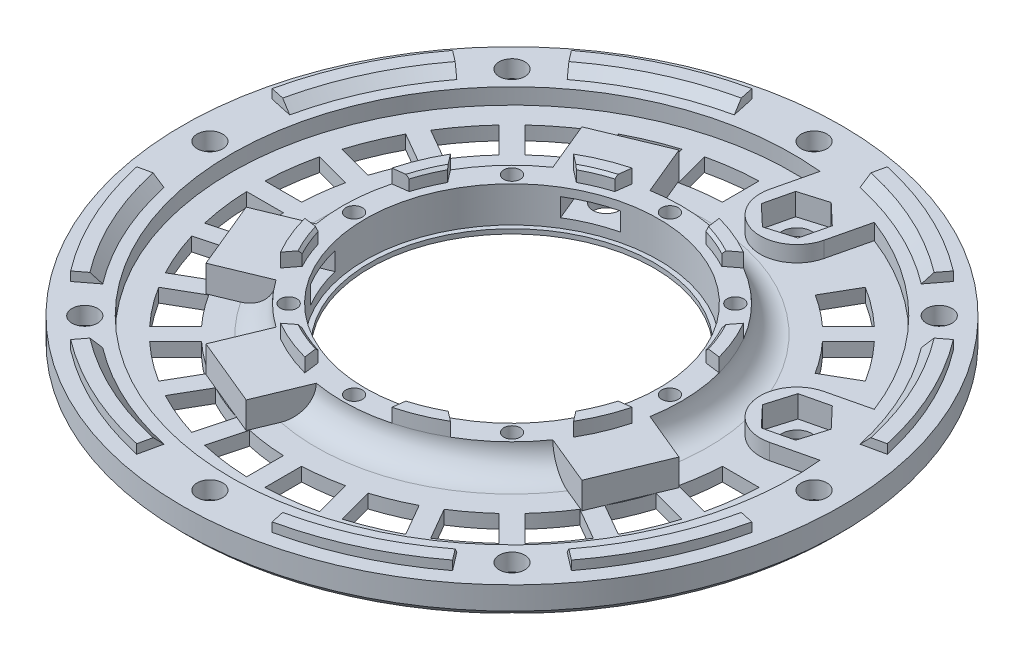
SolidWorks part; units mm, degrees
ref_plane "Front Plane" through (0, 0, 0) normal (0, 0, 1) x (1, 0, 0)
ref_plane "Top Plane" through (0, 0, 0) normal (0, 1, 0) x (1, 0, 0)
ref_plane "Right Plane" through (0, 0, 0) normal (1, 0, 0) x (0, 0, -1)
sketch "Sketch1" plane through (0, 0, 0) normal (0, 1, 0) x (1, 0, 0)
  circle A0 centre (0, 0) radius 16.025
  circle A1 centre (0, 0) radius 36
  dimension "D1" = 32.05
  dimension "D2" = 72
extrude "Boss-Extrude1" add sketch "Sketch1" along normal blind 1
sketch "Sketch2" plane through (0, 0, 0) normal (0, -1, 0) x (1, 0, 0)
  circle A0 centre (0, 0) radius 17.25 construction
  circle A1 centre (0, 0) radius 18.5 construction
  circle A2 centre (0, 0) radius 18.5
  circle A3 centre (0, 0) radius 16.025 construction
  circle A4 centre (0, 0) radius 16.025
  arc A5 (-1.2, 18.461) -> (-4.705, 17.8917) centre (0, 0) ccw construction
  point P3 (0, -17.25)
extrude "Boss-Extrude2" add sketch "Sketch2" against normal offset from surface (3.9 mm away) 3.9 up to face at (0, 0, 36)
fillet "Fillet1" radius 2.9 1 edges at (0, 1, 18.5)
sketch "Sketch4" plane through (0, 0, 0) normal (0, 1, 0) x (1, 0, 0)
  circle A0 centre (0, 0) radius 15.525
  circle A1 centre (0, 0) radius 36
  circle A2 centre (0, 0) radius 36
  circle A3 centre (0, 0) radius 16.025 construction
  dimension "D2" = 0.5
  dimension "D1" = 0
extrude "Boss-Extrude3" add sketch "Sketch4" against normal blind 0.5
sketch "Sketch5" plane through (0, 1, 0) normal (0, 1, 0) x (1, 0, 0)
  line L0 (27.99, -0.75) -> (19.9859, -0.75) construction
  line L1 (19.9859, 0.75) -> (27.99, 0.75) construction
  line L2 (27.99, -0.75) -> (19.9859, -0.75) construction
  line L3 (19.9859, 0.75) -> (27.99, 0.75) construction
  line L4 (0, 0) -> (36, 0) construction
  line L5 (0, 0) -> (34.7733, 9.3175) construction
  line L6 (34.7733, 9.3175) -> (36, 0) construction
  line L7 (0, 0) -> (35.3867, 4.6587) construction
  line L8 (27.99, 1) -> (23.9792, 1)
  line L9 (27.295, 6.2784) -> (23.4209, 5.2403)
  line L10 (27.99, -1) -> (23.9792, -1)
  line L11 (27.295, -6.2784) -> (23.4209, -5.2403)
  line L12 (26.7774, -8.2103) -> (22.9033, -7.1722)
  line L13 (24.74, -13.129) -> (21.2666, -11.1236)
  line L14 (23.74, -14.861) -> (20.2666, -12.8556)
  line L15 (20.499, -19.0848) -> (17.6629, -16.2487)
  line L16 (19.0848, -20.499) -> (16.2487, -17.6629)
  line L17 (14.861, -23.74) -> (12.8556, -20.2666)
  line L18 (13.129, -24.74) -> (11.1236, -21.2666)
  line L19 (8.2103, -26.7774) -> (7.1722, -22.9033)
  line L20 (6.2784, -27.295) -> (5.2403, -23.4209)
  line L21 (1, -27.99) -> (1, -23.9792)
  line L22 (-1, -27.99) -> (-1, -23.9792)
  line L23 (-6.2784, -27.295) -> (-5.2403, -23.4209)
  line L24 (-8.2103, -26.7774) -> (-7.1722, -22.9033)
  line L25 (-13.129, -24.74) -> (-11.1236, -21.2666)
  line L26 (-14.861, -23.74) -> (-12.8556, -20.2666)
  line L27 (-19.0848, -20.499) -> (-16.2487, -17.6629)
  line L28 (-20.499, -19.0848) -> (-17.6629, -16.2487)
  line L29 (-23.74, -14.861) -> (-20.2666, -12.8556)
  line L30 (-24.74, -13.129) -> (-21.2666, -11.1236)
  line L31 (-26.7774, -8.2103) -> (-22.9033, -7.1722)
  line L32 (-27.295, -6.2784) -> (-23.4209, -5.2403)
  line L33 (-27.99, -1) -> (-23.9792, -1)
  line L34 (-27.99, 1) -> (-23.9792, 1)
  line L35 (-27.295, 6.2784) -> (-23.4209, 5.2403)
  line L36 (-26.7774, 8.2103) -> (-22.9033, 7.1722)
  line L37 (-24.74, 13.129) -> (-21.2666, 11.1236)
  line L38 (-23.74, 14.861) -> (-20.2666, 12.8556)
  line L39 (-20.499, 19.0848) -> (-17.6629, 16.2487)
  line L40 (-19.0848, 20.499) -> (-16.2487, 17.6629)
  line L41 (-14.861, 23.74) -> (-12.8556, 20.2666)
  line L42 (-13.129, 24.74) -> (-11.1236, 21.2666)
  line L43 (-8.2103, 26.7774) -> (-7.1722, 22.9033)
  line L44 (-6.2784, 27.295) -> (-5.2403, 23.4209)
  line L45 (-1, 27.99) -> (-1, 23.9792)
  line L46 (1, 27.99) -> (1, 23.9792)
  line L47 (6.2784, 27.295) -> (5.2403, 23.4209)
  line L48 (8.2103, 26.7774) -> (7.1722, 22.9033)
  line L49 (13.129, 24.74) -> (11.1236, 21.2666)
  line L50 (14.861, 23.74) -> (12.8556, 20.2666)
  line L51 (19.0848, 20.499) -> (16.2487, 17.6629)
  line L52 (20.499, 19.0848) -> (17.6629, 16.2487)
  line L53 (23.74, 14.861) -> (20.2666, 12.8556)
  line L54 (24.74, 13.129) -> (21.2666, 11.1236)
  line L55 (26.7774, 8.2103) -> (22.9033, 7.1722)
  line L56 (0, 0) -> (23.9792, 1) construction
  circle A0 centre (0, 0) radius 24 construction
  circle A2 centre (0, 0) radius 36 construction
  arc A3 (23.9792, 1) -> (23.4209, 5.2403) centre (0, 0) ccw
  arc A4 (27.99, 1) -> (27.295, 6.2784) centre (0, 0) ccw
  arc A5 (27.295, -6.2784) -> (27.99, -1) centre (0, 0) ccw
  arc A6 (23.4209, -5.2403) -> (23.9792, -1) centre (0, 0) ccw
  arc A7 (24.74, -13.129) -> (26.7774, -8.2103) centre (0, 0) ccw
  arc A8 (21.2666, -11.1236) -> (22.9033, -7.1722) centre (0, 0) ccw
  arc A9 (20.499, -19.0848) -> (23.74, -14.861) centre (0, 0) ccw
  arc A10 (17.6629, -16.2487) -> (20.2666, -12.8556) centre (0, 0) ccw
  arc A11 (14.861, -23.74) -> (19.0848, -20.499) centre (0, 0) ccw
  arc A12 (12.8556, -20.2666) -> (16.2487, -17.6629) centre (0, 0) ccw
  arc A13 (8.2103, -26.7774) -> (13.129, -24.74) centre (0, 0) ccw
  arc A14 (7.1722, -22.9033) -> (11.1236, -21.2666) centre (0, 0) ccw
  arc A15 (1, -27.99) -> (6.2784, -27.295) centre (0, 0) ccw
  arc A16 (1, -23.9792) -> (5.2403, -23.4209) centre (0, 0) ccw
  arc A17 (-6.2784, -27.295) -> (-1, -27.99) centre (0, 0) ccw
  arc A18 (-5.2403, -23.4209) -> (-1, -23.9792) centre (0, 0) ccw
  arc A19 (-13.129, -24.74) -> (-8.2103, -26.7774) centre (0, 0) ccw
  arc A20 (-11.1236, -21.2666) -> (-7.1722, -22.9033) centre (0, 0) ccw
  arc A21 (-19.0848, -20.499) -> (-14.861, -23.74) centre (0, 0) ccw
  arc A22 (-16.2487, -17.6629) -> (-12.8556, -20.2666) centre (0, 0) ccw
  arc A23 (-23.74, -14.861) -> (-20.499, -19.0848) centre (0, 0) ccw
  arc A24 (-20.2666, -12.8556) -> (-17.6629, -16.2487) centre (0, 0) ccw
  arc A25 (-26.7774, -8.2103) -> (-24.74, -13.129) centre (0, 0) ccw
  arc A26 (-22.9033, -7.1722) -> (-21.2666, -11.1236) centre (0, 0) ccw
  arc A27 (-27.99, -1) -> (-27.295, -6.2784) centre (0, 0) ccw
  arc A28 (-23.9792, -1) -> (-23.4209, -5.2403) centre (0, 0) ccw
  arc A29 (-27.295, 6.2784) -> (-27.99, 1) centre (0, 0) ccw
  arc A30 (-23.4209, 5.2403) -> (-23.9792, 1) centre (0, 0) ccw
  arc A31 (-24.74, 13.129) -> (-26.7774, 8.2103) centre (0, 0) ccw
  arc A32 (-21.2666, 11.1236) -> (-22.9033, 7.1722) centre (0, 0) ccw
  arc A33 (-20.499, 19.0848) -> (-23.74, 14.861) centre (0, 0) ccw
  arc A34 (-17.6629, 16.2487) -> (-20.2666, 12.8556) centre (0, 0) ccw
  arc A35 (-14.861, 23.74) -> (-19.0848, 20.499) centre (0, 0) ccw
  arc A36 (-12.8556, 20.2666) -> (-16.2487, 17.6629) centre (0, 0) ccw
  arc A37 (-8.2103, 26.7774) -> (-13.129, 24.74) centre (0, 0) ccw
  arc A38 (-7.1722, 22.9033) -> (-11.1236, 21.2666) centre (0, 0) ccw
  arc A39 (-1, 27.99) -> (-6.2784, 27.295) centre (0, 0) ccw
  arc A40 (-1, 23.9792) -> (-5.2403, 23.4209) centre (0, 0) ccw
  arc A41 (6.2784, 27.295) -> (1, 27.99) centre (0, 0) ccw
  arc A42 (5.2403, 23.4209) -> (1, 23.9792) centre (0, 0) ccw
  arc A43 (13.129, 24.74) -> (8.2103, 26.7774) centre (0, 0) ccw
  arc A44 (11.1236, 21.2666) -> (7.1722, 22.9033) centre (0, 0) ccw
  arc A45 (19.0848, 20.499) -> (14.861, 23.74) centre (0, 0) ccw
  arc A46 (16.2487, 17.6629) -> (12.8556, 20.2666) centre (0, 0) ccw
  arc A47 (23.74, 14.861) -> (20.499, 19.0848) centre (0, 0) ccw
  arc A48 (20.2666, 12.8556) -> (17.6629, 16.2487) centre (0, 0) ccw
  arc A49 (26.7774, 8.2103) -> (24.74, 13.129) centre (0, 0) ccw
  arc A50 (22.9033, 7.1722) -> (21.2666, 11.1236) centre (0, 0) ccw
  dimension "D1" = 15
  dimension "D2" = 1
  dimension "D4" = 24
  dimension "D3" = 24
extrude "Cut-Extrude1" cut sketch "Sketch5" against normal through all both and the other way through all
sketch "Sketch7" plane through (0, 3.9, 0) normal (0, 1, 0) x (1, 0, 0)
  line L0 (0, 0) -> (0, 17.25) construction
  circle A0 centre (0, 17.25) radius 0.9
  circle A1 centre (12.1976, 12.1976) radius 0.9
  circle A2 centre (17.25, 0) radius 0.9
  circle A3 centre (12.1976, -12.1976) radius 0.9
  circle A4 centre (0, -17.25) radius 0.9
  circle A5 centre (-12.1976, -12.1976) radius 0.9
  circle A6 centre (-17.25, 0) radius 0.9
  circle A7 centre (-12.1976, 12.1976) radius 0.9
  point P21 (0, 0)
  dimension "D1" = 1.8
  dimension "D2" = 8
extrude "Cut-Extrude2" cut sketch "Sketch7" against normal through all
sketch "Sketch8" plane through (0, 1, 0) normal (0, 1, 0) x (1, 0, 0)
  arc A0 (-30.6392, -0.8144) -> (-29.9521, -6.5032) centre (0, 0) ccw construction
  arc A1 (-30.6392, -0.8144) -> (-29.9521, -6.5032) centre (0, 0) ccw construction
  arc A2 (-29.9521, 6.5032) -> (-30.6392, 0.8144) centre (0, 0) ccw construction
  arc A3 (-29.9521, 6.5032) -> (-30.6392, 0.8144) centre (0, 0) ccw construction
  circle A5 centre (0, 0) radius 30.65
  circle A6 centre (0, 0) radius 36 construction
  circle A7 centre (0, 0) radius 36
extrude "Boss-Extrude4" add sketch "Sketch8" along normal blind 1.7378
sketch "Sketch9" plane through (0, 2.7378, 0) normal (0, 1, 0) x (1, 0, 0)
  line L0 (0, 0) -> (-29.9521, 6.5032) construction
  line L1 (0, 0) -> (-29.9521, -6.5032) construction
  line L2 (-29.9521, 6.5032) -> (-29.9521, -6.5032) construction
  line L3 (-27.3707, 21.0023) -> (-23.9196, 18.3542) construction
  line L4 (0, 0) -> (0, 36) construction
  line L5 (0, 0) -> (-25.4558, 25.4558) construction
  line L6 (-24.3163, 18.6585) -> (0, 0) construction
  line L7 (-24.3163, 18.6585) -> (-28.5607, 21.9154) construction
  line L8 (-29.9521, 6.5032) -> (-35.1803, 7.6384) construction
  line L9 (-27.3521, 20.862) -> (-25.3687, 19.3401)
  line L10 (-31.2086, 14.47) -> (0, 0) construction
  line L11 (-33.5954, 7.3966) -> (-31.1523, 6.8662)
  line L12 (-7.3966, 33.5954) -> (-6.8662, 31.1523)
  line L13 (-20.862, 27.3521) -> (-19.3401, 25.3687)
  arc A0 (-29.9521, 6.5032) -> (-24.3163, 18.6585) centre (0, 0) cw construction
  arc A1 (-35.1803, 7.6384) -> (-28.5607, 21.9154) centre (0, 0) cw construction
  circle A2 centre (0, 0) radius 36 construction
  circle A3 centre (0, 0) radius 30.65 construction
  arc A4 (-27.2914, 20.9414) -> (-33.6168, 7.2989) centre (0, 0) ccw construction
  arc A5 (-31.1523, 6.8662) -> (-25.3687, 19.3401) centre (0, 0) cw
  arc A6 (-33.5954, 7.3966) -> (-27.3521, 20.862) centre (0, 0) cw
  circle A7 centre (0, 0) radius 36 construction
  arc A8 (-6.8662, 31.1523) -> (-19.3401, 25.3687) centre (0, 0) ccw
  arc A9 (-7.3966, 33.5954) -> (-20.862, 27.3521) centre (0, 0) ccw
  dimension "D2" = 0.1
  dimension "D3" = 45
  dimension "D4" = 0.1
  dimension "D1" = 2.5
extrude "Boss-Extrude5" add sketch "Sketch9" along normal blind 1
ref_axis "Axis1" through (0, -0.72, 0) along (0, 1, 0)
pattern_circular "CirPattern1" count 4 over 360 about axis through (0, -0.72, 0) along (0, 1, 0) of "Boss-Extrude5"
chamfer "Chamfer1" distance 1 angle 45 8 edges at (-28.9406, 3.7378, -13.4184) (-13.4184, 3.7378, -28.9406) (13.4184, 3.7378, -28.9406) (28.9406, 3.7378, -13.4184) (28.9406, 3.7378, 13.4184) (13.4184, 3.7378, 28.9406) (-13.4184, 3.7378, 28.9406) (-28.9406, 3.7378, 13.4184)
sketch "Sketch10" plane through (0, 2.7378, 0) normal (0, 1, 0) x (1, 0, 0)
  line L0 (0, 0) -> (0, 36) construction
  circle A0 centre (0, 0) radius 36 construction
  circle A1 centre (0, 33) radius 1.4 construction
  circle A2 centre (0, 33) radius 1.4
  circle A3 centre (23.3345, 23.3345) radius 1.4
  circle A4 centre (33, 0) radius 1.4
  circle A5 centre (23.3345, -23.3345) radius 1.4
  circle A6 centre (0, -33) radius 1.4
  circle A7 centre (-23.3345, -23.3345) radius 1.4
  circle A8 centre (-33, 0) radius 1.4
  circle A9 centre (-23.3345, 23.3345) radius 1.4
  point P26 (0, 0)
  dimension "D1" = 8
extrude "Cut-Extrude3" cut sketch "Sketch10" against normal through all both and the other way through all
chamfer "Chamfer2" distance 0.75 angle 45 1 edges at (0, -0.5, 36)
hole_wizard "CSK for M2.5 Flat Head Machine Screw1" positions "Sketch11" profile "Sketch12" countersink size "M2.5" standard "ANSI Metric" end condition through all
sketch "Sketch11" plane through (0, -0.5, 0) normal (0, -1, 0) x (-1, 0, 0)
  point P0 (0, -33)
  point P3 (23.3345, -23.3345)
  point P6 (33, 0)
  point P9 (23.3345, 23.3345)
  point P12 (0, 33)
  point P15 (-23.3345, 23.3345)
  point P18 (-33, 0)
  point P21 (-23.3345, -23.3345)
sketch "Sketch12" plane through (0, -0.5, 33) normal (1, 0, 0) x (0, 0, -1)
  line L0 (0, 0) -> (0, 4.4)
  line L1 (0, 4.4) -> (1.35, 4.4)
  line L2 (1.35, 4.4) -> (1.35, 1.4)
  line L3 (1.35, 1.4) -> (2.75, 0)
  line L5 (2.75, 0) -> (0, 0)
  line L6 (-1.35, 1.4) -> (-2.75, 0) construction
  line L11 (0, -6.35) -> (0, 107.95) construction
  dimension "Thru Hole Dia." = 2.7
  dimension "Thru Hole Depth" = 4.4
  dimension "Near C'Sink Dia." = 5.5
  dimension "Near C'Sink Angle" = 90
sketch "Sketch13" plane through (0, 3.9, 0) normal (0, 1, 0) x (1, 0, 0)
  line L0 (0, 0) -> (-7.0796, 17.0918) construction
  line L1 (0, 0) -> (0, 18.5) construction
  line L2 (-9.2808, 16.0037) -> (-7.9403, 14.9751)
  line L3 (-4.7538, 17.8788) -> (-4.9743, 16.2037)
  line L4 (4.7538, 17.8788) -> (4.9743, 16.2037)
  line L5 (9.2808, 16.0037) -> (7.9403, 14.9751)
  line L6 (16.0037, 9.2808) -> (14.9751, 7.9403)
  line L7 (17.8788, 4.7538) -> (16.2037, 4.9743)
  line L8 (17.8788, -4.7538) -> (16.2037, -4.9743)
  line L9 (16.0037, -9.2808) -> (14.9751, -7.9403)
  line L10 (9.2808, -16.0037) -> (7.9403, -14.9751)
  line L11 (4.7538, -17.8788) -> (4.9743, -16.2037)
  line L12 (-4.7538, -17.8788) -> (-4.9743, -16.2037)
  line L13 (-9.2808, -16.0037) -> (-7.9403, -14.9751)
  line L14 (-16.0037, -9.2808) -> (-14.9751, -7.9403)
  line L15 (-17.8788, -4.7538) -> (-16.2037, -4.9743)
  line L16 (-17.8788, 4.7538) -> (-16.2037, 4.9743)
  line L17 (-16.0037, 9.2808) -> (-14.9751, 7.9403)
  circle A0 centre (0, 0) radius 18.5 construction
  arc A1 (-7.9403, 14.9751) -> (-4.9743, 16.2037) centre (0, 0) cw
  arc A2 (-9.2808, 16.0037) -> (-4.7538, 17.8788) centre (0, 0) cw
  arc A3 (4.9743, 16.2037) -> (7.9403, 14.9751) centre (0, 0) cw
  arc A4 (4.7538, 17.8788) -> (9.2808, 16.0037) centre (0, 0) cw
  arc A5 (14.9751, 7.9403) -> (16.2037, 4.9743) centre (0, 0) cw
  arc A6 (16.0037, 9.2808) -> (17.8788, 4.7538) centre (0, 0) cw
  arc A7 (16.2037, -4.9743) -> (14.9751, -7.9403) centre (0, 0) cw
  arc A8 (17.8788, -4.7538) -> (16.0037, -9.2808) centre (0, 0) cw
  arc A9 (7.9403, -14.9751) -> (4.9743, -16.2037) centre (0, 0) cw
  arc A10 (9.2808, -16.0037) -> (4.7538, -17.8788) centre (0, 0) cw
  arc A11 (-4.9743, -16.2037) -> (-7.9403, -14.9751) centre (0, 0) cw
  arc A12 (-4.7538, -17.8788) -> (-9.2808, -16.0037) centre (0, 0) cw
  arc A13 (-14.9751, -7.9403) -> (-16.2037, -4.9743) centre (0, 0) cw
  arc A14 (-16.0037, -9.2808) -> (-17.8788, -4.7538) centre (0, 0) cw
  arc A15 (-16.2037, 4.9743) -> (-14.9751, 7.9403) centre (0, 0) cw
  arc A16 (-17.8788, 4.7538) -> (-16.0037, 9.2808) centre (0, 0) cw
  point P12 (-6.4865, 15.6598)
  point P20 (6.4865, 15.6598)
  point P25 (15.6598, 6.4865)
  point P30 (15.6598, -6.4865)
  point P35 (6.4865, -15.6598)
  point P40 (-6.4865, -15.6598)
  point P45 (-15.6598, -6.4865)
  point P50 (-15.6598, 6.4865)
  point P51 (0, 0)
  dimension "D1" = 22.5
  dimension "D2" = 30
  dimension "D3" = 1.55
  dimension "D4" = 4.9
  dimension "D5" = 8
extrude "Boss-Extrude6" add sketch "Sketch13" along normal blind 1.5
chamfer "Chamfer3" distance 0.3 angle 45 8 edges at (-15.6598, 5.4, -6.4865) (-15.6598, 5.4, 6.4865) (-6.4865, 5.4, 15.6598) (6.4865, 5.4, 15.6598) (15.6598, 5.4, 6.4865) (15.6598, 5.4, -6.4865) (6.4865, 5.4, -15.6598) (-6.4865, 5.4, -15.6598)
sketch "Sketch14" plane through (0, -0.5, 0) normal (0, -1, 0) x (1, 0, 0)
  line L0 (0, 0) -> (25.4558, -25.4558) construction
  line L1 (0, 0) -> (0, -36) construction
  line L6 (0, 0) -> (-22.1731, 9.1844) construction
  line L7 (0, 0) -> (-9.1844, -22.1731) construction
  circle A0 centre (0, 0) radius 36 construction
  circle A1 centre (0, 0) radius 16.025 construction
  arc A5 (-21.2666, 11.1236) -> (-22.9033, 7.1722) centre (0, 0) ccw construction
  circle A6 centre (-17.5768, 7.2806) radius 1.45
  circle A7 centre (-17.5768, 7.2806) radius 4.975 construction
  arc A8 (-11.1236, -21.2666) -> (-7.1722, -22.9033) centre (0, 0) ccw construction
  circle A9 centre (-7.2806, -17.5768) radius 1.45
  circle A10 centre (-7.2806, -17.5768) radius 4.975 construction
  circle A11 centre (17.5768, 7.2806) radius 1.45
  circle A12 centre (-7.2806, 17.5768) radius 1.45
  point P24 (0, 0)
  point P25 (-14.8052, 6.1325)
  point P28 (-16.2372, 6.7257)
  dimension "D2" = 2.9
  dimension "D3" = 3
  dimension "D1" = 45
sketch "Sketch15" plane through (0, 1, 0) normal (0, 1, 0) x (1, 0, 0)
  line L0 (-9.8825, 13.2519) -> (-12.8979, 20.5316)
  line L1 (-9.8825, 13.2519) -> (-2.3825, 16.3585)
  line L2 (-12.8979, 20.5316) -> (-5.3979, 23.6382)
  line L3 (-2.3825, 16.3585) -> (-5.3979, 23.6382)
  line L4 (-9.8825, 13.2519) -> (-5.3979, 23.6382) construction
  line L5 (-12.8979, 20.5316) -> (-2.3825, 16.3585) construction
  line L6 (0, 0) -> (-9.1844, 22.1731) construction
  line L7 (2.3825, 16.3585) -> (5.3979, 23.6382) [skipped]
  line L8 (2.3825, 16.3585) -> (9.8825, 13.2519) [skipped]
  line L9 (5.3979, 23.6382) -> (12.8979, 20.5316) [skipped]
  line L10 (9.8825, 13.2519) -> (12.8979, 20.5316) [skipped]
  line L11 (2.3825, 16.3585) -> (12.8979, 20.5316) construction
  line L12 (5.3979, 23.6382) -> (9.8825, 13.2519) construction
  line L13 (13.2519, 9.8825) -> (20.5316, 12.8979) [skipped]
  line L14 (13.2519, 9.8825) -> (16.3585, 2.3825) [skipped]
  line L15 (20.5316, 12.8979) -> (23.6382, 5.3979) [skipped]
  line L16 (16.3585, 2.3825) -> (23.6382, 5.3979) [skipped]
  line L17 (13.2519, 9.8825) -> (23.6382, 5.3979) construction
  line L18 (20.5316, 12.8979) -> (16.3585, 2.3825) construction
  line L19 (16.3585, -2.3825) -> (23.6382, -5.3979)
  line L20 (16.3585, -2.3825) -> (13.2519, -9.8825)
  line L21 (23.6382, -5.3979) -> (20.5316, -12.8979)
  line L22 (13.2519, -9.8825) -> (20.5316, -12.8979)
  line L23 (16.3585, -2.3825) -> (20.5316, -12.8979) construction
  line L24 (23.6382, -5.3979) -> (13.2519, -9.8825) construction
  line L25 (9.8825, -13.2519) -> (12.8979, -20.5316) [skipped]
  line L26 (9.8825, -13.2519) -> (2.3825, -16.3585) [skipped]
  line L27 (12.8979, -20.5316) -> (5.3979, -23.6382) [skipped]
  line L28 (2.3825, -16.3585) -> (5.3979, -23.6382) [skipped]
  line L29 (9.8825, -13.2519) -> (5.3979, -23.6382) construction
  line L30 (12.8979, -20.5316) -> (2.3825, -16.3585) construction
  line L31 (-2.3825, -16.3585) -> (-5.3979, -23.6382)
  line L32 (-2.3825, -16.3585) -> (-9.8825, -13.2519)
  line L33 (-5.3979, -23.6382) -> (-12.8979, -20.5316)
  line L34 (-9.8825, -13.2519) -> (-12.8979, -20.5316)
  line L35 (-2.3825, -16.3585) -> (-12.8979, -20.5316) construction
  line L36 (-5.3979, -23.6382) -> (-9.8825, -13.2519) construction
  line L37 (-13.2519, -9.8825) -> (-20.5316, -12.8979)
  line L38 (-13.2519, -9.8825) -> (-16.3585, -2.3825)
  line L39 (-20.5316, -12.8979) -> (-23.6382, -5.3979)
  line L40 (-16.3585, -2.3825) -> (-23.6382, -5.3979)
  line L41 (-13.2519, -9.8825) -> (-23.6382, -5.3979) construction
  line L42 (-20.5316, -12.8979) -> (-16.3585, -2.3825) construction
  line L43 (-16.3585, 2.3825) -> (-23.6382, 5.3979) [skipped]
  line L44 (-16.3585, 2.3825) -> (-13.2519, 9.8825) [skipped]
  line L45 (-23.6382, 5.3979) -> (-20.5316, 12.8979) [skipped]
  line L46 (-13.2519, 9.8825) -> (-20.5316, 12.8979) [skipped]
  line L47 (-16.3585, 2.3825) -> (-20.5316, 12.8979) construction
  line L48 (-23.6382, 5.3979) -> (-13.2519, 9.8825) construction
  line L49 (0, 0) -> (-9.1844, 22.1731) construction
  arc A1 (-7.1722, 22.9033) -> (-11.1236, 21.2666) centre (0, 0) ccw construction
  circle A2 centre (0, 0) radius 16.025 construction
  point P1 (-7.6402, 18.445)
  point P9 (7.6402, 18.445)
  point P18 (18.445, 7.6402)
  point P23 (18.445, -7.6402)
  point P28 (7.6402, -18.445)
  point P33 (-7.6402, -18.445)
  point P38 (-18.445, -7.6402)
  point P43 (-18.445, 7.6402)
  point P48 (0, 0)
  dimension "D1" = 7.5
  dimension "D2" = 8
extrude "Boss-Extrude7" add sketch "Sketch15" along normal up to surface (2.9 mm away) up to face at (0, 3.9, -16.35)
extrude "Cut-Extrude4" cut sketch "Sketch14" against normal blind 3.5
sketch "Sketch16" plane through (0, -0.5, 0) normal (0, -1, 0) x (1, 0, 0)
  line L0 (0, 0) -> (23.3345, -23.3345) construction
  line L1 (10.1026, 7.7782) -> (22.348, -8.1266) construction
  line L2 (0, 0) -> (0, -17.25) construction
  line L3 (0, 0) -> (10.1026, 7.7782) construction
  line L4 (18.6021, 8.3059) -> (13.454, 13.454) construction
  line L5 (0, 0) -> (13.454, 13.454) construction
  line L6 (25.1212, -5.9915) -> (27.5961, -3.5166) construction
  line L7 (27.5961, -3.5166) -> (12.0398, 12.0398) construction
  circle A0 centre (0, 0) radius 12.75 construction
  circle A1 centre (25.1212, -5.9915) radius 1.65
  circle A2 centre (25.1212, -5.9915) radius 3.5 construction
  circle A3 centre (17.5768, 7.2806) radius 1.45 construction
  circle A4 centre (5.9915, -25.1212) radius 1.65
  dimension "D1" = 25.5
  dimension "D2" = 3.3
  dimension "D3" = 7
  dimension "D4" = 2
  dimension "D5" = 22
sketch "Sketch17" plane through (0, -0.5, 0) normal (0, -1, 0) x (1, 0, 0)
  line L0 (24.74, -13.129) -> (21.2666, -11.1236) construction
  line L1 (24.74, -13.129) -> (21.2666, -11.1236)
  line L2 (0, 0) -> (12.1976, -12.1976) construction
  line L3 (13.129, -24.74) -> (11.1236, -21.2666)
  arc A0 (21.2666, -11.1236) -> (22.9033, -7.1722) centre (0, 0) ccw construction
  arc A1 (24.74, -13.129) -> (26.7774, -8.2103) centre (0, 0) ccw construction
  arc A4 (21.2666, -11.1236) -> (21.5701, -10.5228) centre (0, 0) ccw
  arc A5 (24.74, -13.129) -> (25.4284, -11.7403) centre (0, 0) ccw
  arc A8 (25.4284, -11.7403) -> (21.5701, -10.5228) centre (25.1212, -5.9915) ccw
  arc A9 (11.7403, -25.4284) -> (10.5228, -21.5701) centre (5.9915, -25.1212) cw
  arc A10 (13.129, -24.74) -> (11.7403, -25.4284) centre (0, 0) cw
  arc A11 (11.1236, -21.2666) -> (10.5228, -21.5701) centre (0, 0) cw
extrude "Boss-Extrude8" add sketch "Sketch17" against normal up to surface (1.5 mm away) up to face at (25.7264, 1, -3.3869)
sketch "Sketch18" plane through (0, 1, 0) normal (0, 1, 0) x (1, 0, 0)
  line L0 (0, 0) -> (25.1212, 5.9915) construction
  line L1 (24.1933, 9.8823) -> (28.6308, 10.9407)
  line L2 (26.0492, 2.1006) -> (30.4868, 3.1589)
  line L3 (0, 0) -> (23.3345, 23.3345) construction
  line L4 (9.8823, 24.1933) -> (10.9407, 28.6308)
  line L5 (2.1006, 26.0492) -> (3.1589, 30.4868)
  arc A0 (24.1933, 9.8823) -> (26.0492, 2.1006) centre (25.1212, 5.9915) ccw
  circle A1 centre (0, 0) radius 30.65 construction
  circle A2 centre (0, 0) radius 30.65 construction
  arc A3 (30.4868, 3.1589) -> (28.6308, 10.9407) centre (0, 0) ccw
  arc A4 (3.1589, 30.4868) -> (10.9407, 28.6308) centre (0, 0) cw
  arc A5 (9.8823, 24.1933) -> (2.1006, 26.0492) centre (5.9915, 25.1212) cw
  dimension "D1" = 8
extrude "Boss-Extrude9" add sketch "Sketch18" along normal up to surface (1.7378 mm away) up to face at (0, 2.7378, -31.6)
extrude "Cut-Extrude5" cut sketch "Sketch16" against normal through all
sketch "Sketch19" plane through (0, 2.7378, 0) normal (0, 1, 0) x (1, 0, 0)
  line L0 (0, 0) -> (25.1212, 5.9915) construction
  line L1 (28.1539, 6.7147) -> (26.0112, 8.9794)
  line L2 (26.0112, 8.9794) -> (22.9785, 8.2561)
  line L3 (22.9785, 8.2561) -> (22.0886, 5.2682)
  line L4 (22.0886, 5.2682) -> (24.2313, 3.0035)
  line L5 (24.2313, 3.0035) -> (27.2639, 3.7268)
  line L6 (27.2639, 3.7268) -> (28.1539, 6.7147)
  line L7 (0, 0) -> (23.3345, 23.3345) construction
  line L8 (3.7268, 27.2639) -> (6.7147, 28.1539)
  line L9 (3.0035, 24.2313) -> (3.7268, 27.2639)
  line L10 (5.2682, 22.0886) -> (3.0035, 24.2313)
  line L11 (8.2561, 22.9785) -> (5.2682, 22.0886)
  line L12 (8.9794, 26.0112) -> (8.2561, 22.9785)
  line L13 (6.7147, 28.1539) -> (8.9794, 26.0112)
  circle A0 centre (25.1212, 5.9915) radius 2.7 construction
  dimension "D1" = 5.4
extrude "Cut-Extrude6" cut sketch "Sketch19" against normal blind 2.4
sketch "Sketch20" plane through (0, 3, 0) normal (0, -1, 0) x (1, 0, 0)
  line L0 (0, 0) -> (-17.5768, 7.2806) construction
  line L5 (-15.2866, 9.0379) -> (-13.6672, 8.3671)
  line L6 (-14.9098, 6.1758) -> (-15.2866, 9.0379) construction
  line L16 (-15.2866, 9.0379) -> (-17.9536, 10.1426)
  line L17 (-17.9536, 10.1426) -> (-20.2438, 8.3853)
  line L18 (-20.2438, 8.3853) -> (-19.867, 5.5232)
  line L19 (-19.867, 5.5232) -> (-17.2, 4.4185)
  line L20 (-17.2, 4.4185) -> (-14.9098, 6.1758) construction
  line L21 (-13.6672, 8.3671) -> (-15.5806, 3.7477)
  line L28 (-15.5806, 3.7477) -> (-17.2, 4.4185)
  line L29 (-8.3671, 13.6672) -> (-9.0379, 15.2866)
  line L30 (-10.1426, 17.9536) -> (-9.0379, 15.2866)
  line L31 (-8.3853, 20.2438) -> (-10.1426, 17.9536)
  line L32 (-5.5232, 19.867) -> (-8.3853, 20.2438)
  line L33 (-4.4185, 17.2) -> (-5.5232, 19.867)
  line L34 (-4.4185, 17.2) -> (-3.7477, 15.5806)
  line L35 (-3.7477, 15.5806) -> (-8.3671, 13.6672)
  line L36 (3.7477, 15.5806) -> (4.4185, 17.2) [skipped]
  line L37 (5.5232, 19.867) -> (4.4185, 17.2) [skipped]
  line L38 (8.3853, 20.2438) -> (5.5232, 19.867) [skipped]
  line L39 (10.1426, 17.9536) -> (8.3853, 20.2438) [skipped]
  line L46 (9.0379, 15.2866) -> (10.1426, 17.9536) [skipped]
  line L47 (9.0379, 15.2866) -> (8.3671, 13.6672) [skipped]
  line L48 (8.3671, 13.6672) -> (3.7477, 15.5806) [skipped]
  line L49 (13.6672, 8.3671) -> (15.2866, 9.0379)
  line L50 (17.9536, 10.1426) -> (15.2866, 9.0379)
  line L51 (20.2438, 8.3853) -> (17.9536, 10.1426)
  line L52 (19.867, 5.5232) -> (20.2438, 8.3853)
  line L53 (17.2, 4.4185) -> (19.867, 5.5232)
  line L54 (17.2, 4.4185) -> (15.5806, 3.7477)
  line L55 (15.5806, 3.7477) -> (13.6672, 8.3671)
  line L56 (15.5806, -3.7477) -> (17.2, -4.4185) [skipped]
  line L57 (19.867, -5.5232) -> (17.2, -4.4185) [skipped]
  line L58 (20.2438, -8.3853) -> (19.867, -5.5232) [skipped]
  line L59 (17.9536, -10.1426) -> (20.2438, -8.3853) [skipped]
  line L60 (15.2866, -9.0379) -> (17.9536, -10.1426) [skipped]
  line L61 (15.2866, -9.0379) -> (13.6672, -8.3671) [skipped]
  line L62 (13.6672, -8.3671) -> (15.5806, -3.7477) [skipped]
  line L63 (8.3671, -13.6672) -> (9.0379, -15.2866) [skipped]
  line L64 (10.1426, -17.9536) -> (9.0379, -15.2866) [skipped]
  line L65 (8.3853, -20.2438) -> (10.1426, -17.9536) [skipped]
  line L66 (5.5232, -19.867) -> (8.3853, -20.2438) [skipped]
  line L67 (4.4185, -17.2) -> (5.5232, -19.867) [skipped]
  line L68 (4.4185, -17.2) -> (3.7477, -15.5806) [skipped]
  line L69 (3.7477, -15.5806) -> (8.3671, -13.6672) [skipped]
  line L70 (-3.7477, -15.5806) -> (-4.4185, -17.2)
  line L71 (-5.5232, -19.867) -> (-4.4185, -17.2)
  line L72 (-8.3853, -20.2438) -> (-5.5232, -19.867)
  line L73 (-10.1426, -17.9536) -> (-8.3853, -20.2438)
  line L74 (-9.0379, -15.2866) -> (-10.1426, -17.9536)
  line L75 (-9.0379, -15.2866) -> (-8.3671, -13.6672)
  line L76 (-8.3671, -13.6672) -> (-3.7477, -15.5806)
  line L77 (-13.6672, -8.3671) -> (-15.2866, -9.0379) [skipped]
  line L78 (-17.9536, -10.1426) -> (-15.2866, -9.0379) [skipped]
  line L79 (-20.2438, -8.3853) -> (-17.9536, -10.1426) [skipped]
  line L80 (-19.867, -5.5232) -> (-20.2438, -8.3853) [skipped]
  line L81 (-17.2, -4.4185) -> (-19.867, -5.5232) [skipped]
  line L82 (-17.2, -4.4185) -> (-15.5806, -3.7477) [skipped]
  line L83 (-15.5806, -3.7477) -> (-13.6672, -8.3671) [skipped]
  circle A1 centre (-17.5768, 7.2806) radius 2.5 construction
  circle A3 centre (0, 0) radius 16.025 construction
  point P4 (0, 0)
  point P14 (0, 0)
  point P57 (0, 0)
  point P69 (0, 0)
  dimension "D1" = 5
extrude "Cut-Extrude7" cut sketch "Sketch20" along normal blind 2
ref_plane "Plane1" through (0.6364, 0, 0.6364) normal (-0.7071, 0, -0.7071) x (-0.7071, 0, 0.7071)
